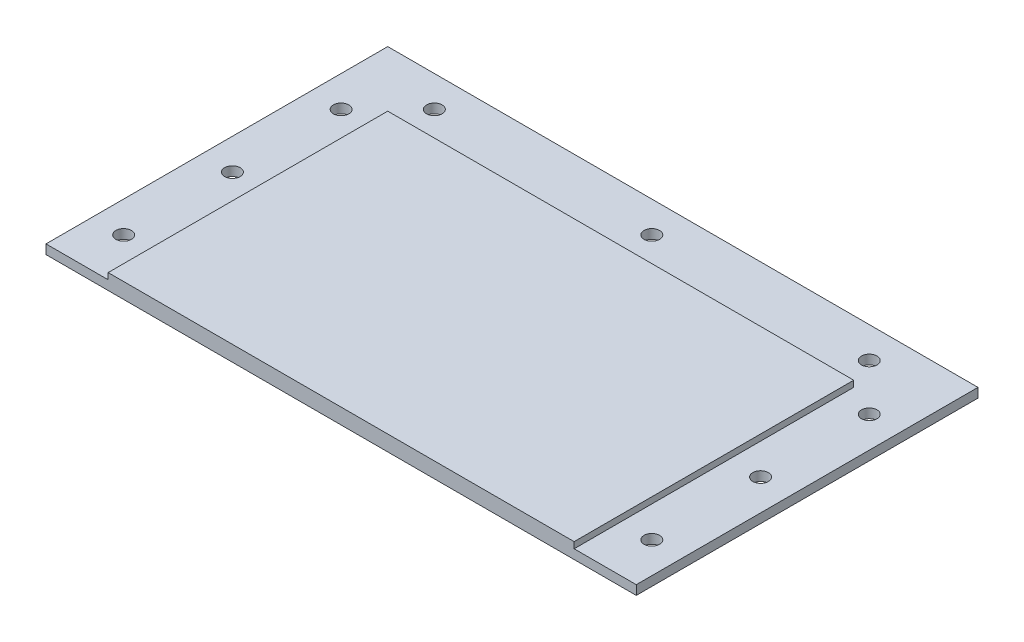
SolidWorks part; units mm, degrees
ref_plane "Alzado" through (0, 0, 0) normal (0, 0, 1) x (1, 0, 0)
ref_plane "Planta" through (0, 0, 0) normal (0, 1, 0) x (1, 0, 0)
ref_plane "Vista lateral" through (0, 0, 0) normal (1, 0, 0) x (0, 0, -1)
sketch "Croquis1" plane through (0, 0, 0) normal (0, 1, 0) x (1, 0, 0)
  line L1 (-75, 45) -> (75, 45)
  line L2 (-75, 45) -> (-75, -45)
  line L3 (-75, -45) -> (75, -45)
  line L4 (75, 45) -> (75, -45)
  line L5 (-75, 45) -> (75, -45) construction
  line L6 (-75, -45) -> (75, 45) construction
  line L12 (-95, -45) -> (95, -45)
  line L13 (-95, -45) -> (-95, 65)
  line L14 (-95, 65) -> (95, 65)
  line L15 (95, -45) -> (95, 65)
  point P0 (0, 0)
  point P6 (0, 0)
  dimension "D1" = 150
  dimension "D2" = 90
  dimension "D3" = 110
  dimension "D4" = 190
  dimension "D5" = 20
extrude "Saliente-Extruir1" add sketch "Croquis1" along normal blind 5 contours L4 L1 L2 L3 | L2 L1 L4 L3 region at (0, 0, 0)
extrude "Saliente-Extruir2" add sketch "Croquis1<3>" along normal blind 3 contours L12 L15 L14 L13 L2 L1 L4 region at (-77.1954, 0, 0)
sketch "Croquis1<3>" plane through (0, 0, 0) normal (0, 1, 0) x (1, 0, 0) same geometry as "Croquis1"
sketch "Croquis2" plane through (0, 0, 0) normal (0, -1, 0) x (1, 0, 0)
  line L0 (85, -65) -> (85, 45) construction
  line L1 (-95, -65) -> (95, -65) construction
  line L2 (-95, 45) -> (95, 45) construction
  line L3 (95, -55) -> (-95, -55) construction
  line L4 (95, 45) -> (95, -65) construction
  line L5 (-95, 45) -> (-95, -65) construction
  line L6 (-85, -65) -> (-85, 45) construction
  circle A9 centre (85, 30) radius 2.5
  circle A10 centre (70, -55) radius 2.5
  circle A11 centre (-85, -40) radius 2.5
  circle A12 centre (-85, -5) radius 2.5
  circle A13 centre (-85, 30) radius 2.5
  circle A14 centre (0, -55) radius 2.5
  circle A15 centre (-70, -55) radius 2.5
  circle A16 centre (85, -5) radius 2.5
  circle A17 centre (85, -40) radius 2.5
  dimension "D2" = 10
  dimension "D7" = 5
  dimension "D8" = 5
  dimension "D9" = 5
  dimension "D10" = 15
  dimension "D1" = 10
  dimension "D3" = 10
  dimension "D4" = 3
  dimension "D5" = 3
  dimension "D6" = 3
  dimension "D11" = 15
  dimension "D12" = 15
  dimension "D13" = 15
  dimension "D14" = 15
  dimension "D15" = 15
extrude "Cortar-Extruir1" cut sketch "Croquis2" against normal blind 10
